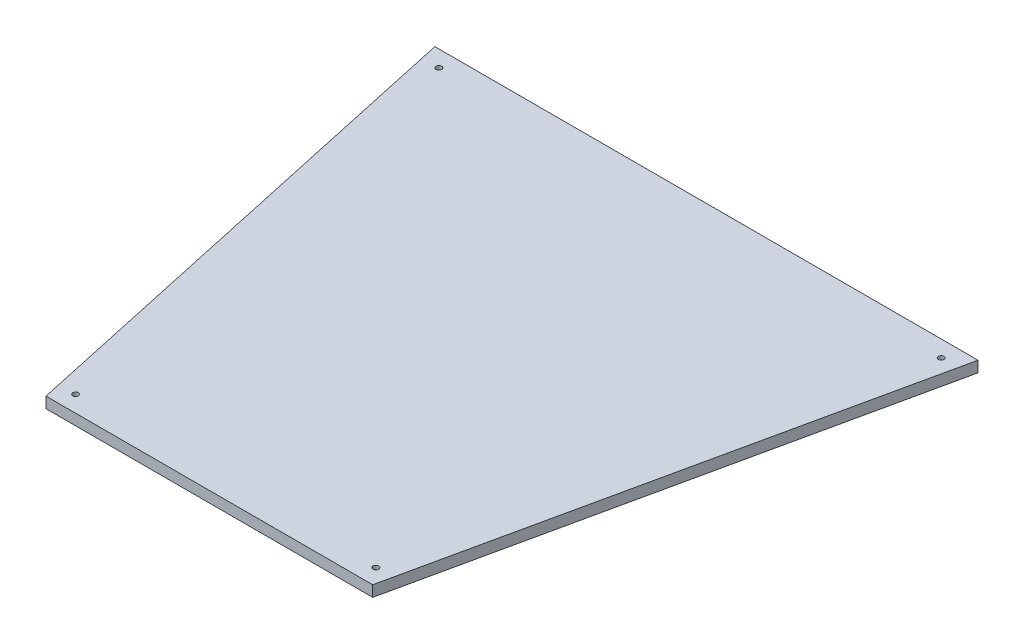
SolidWorks part; units mm, degrees
ref_plane "Front Plane" through (0, 0, 0) normal (0, 0, 1) x (1, 0, 0)
ref_plane "Top Plane" through (0, 0, 0) normal (0, 1, 0) x (1, 0, 0)
ref_plane "Right Plane" through (0, 0, 0) normal (1, 0, 0) x (0, 0, -1)
ref_plane "Plane1" through (0, 1.8029, 0.0014) normal (0, -1, -0.0008) x (-1, 0, 0)
sketch "Sketch1" plane through (4.556, 0, 422.8773) normal (0, -1, 0) x (-1, 0, 0)
  line L0 (-184.8912, -195.6633) -> (194.0158, -195.651)
  line L1 (194.0158, -195.651) -> (319.5098, 380.9014)
  line L2 (319.5098, 380.9014) -> (-310.4225, 380.881)
  line L3 (-310.4225, 380.881) -> (-184.8912, -195.6633)
  line L4 (-310.424, 380.881) -> (319.5114, 380.9014) construction
  line L5 (-184.7475, -196.3231) -> (-311.7795, 387.1134) construction
  line L6 (320.8664, 387.1339) -> (193.8722, -196.3108) construction
  line L7 (194.0186, -195.651) -> (-184.8939, -195.6633) construction
extrude "Boss-Extrude1" add sketch "Sketch1" along normal blind 12.7
sketch "Sketch2" plane through (0, 0, 0) normal (0, 1, 0) x (1, 0, 0)
  circle A28 centre (-174.1239, -599.479) radius 3.2639
  circle A30 centre (-174.1239, -599.479) radius 3.2639
  circle A32 centre (174.085, -599.4903) radius 3.2639
  circle A33 centre (174.085, -599.4903) radius 3.2639
  circle A34 centre (291.3209, -61.0456) radius 3.2639
  circle A35 centre (291.3209, -61.0456) radius 3.2639
  circle A36 centre (-291.3249, -61.0268) radius 3.2639
  circle A37 centre (-291.3249, -61.0268) radius 3.2639
  dimension "D7" = 0
  dimension "D8" = 0
  dimension "D9" = 0
  dimension "D13" = 0
extrude "Cut-Extrude1" cut sketch "Sketch2" against normal through all
